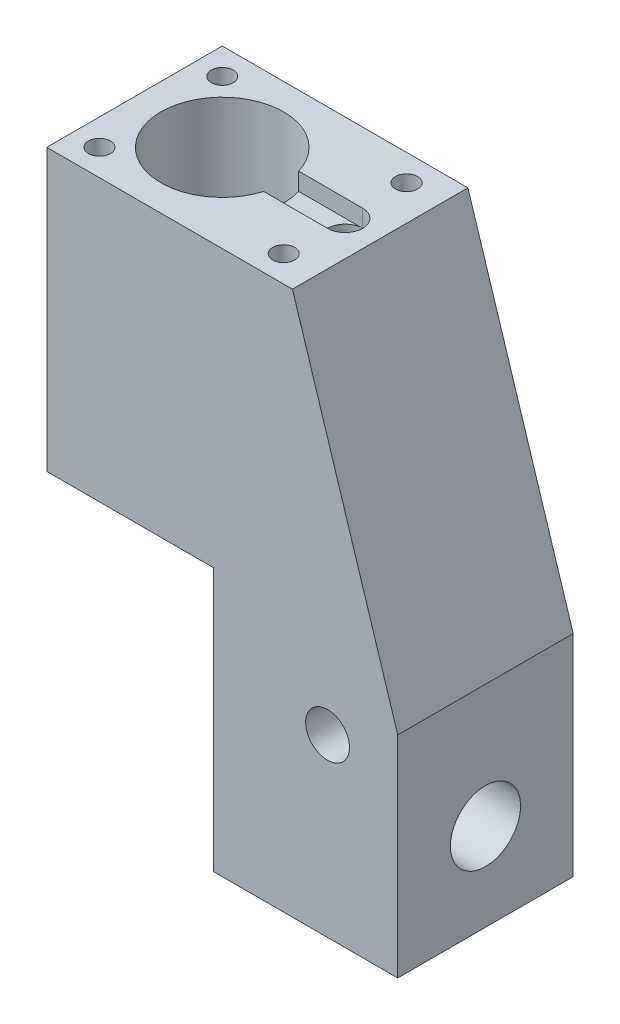
SolidWorks part; units mm, degrees
ref_plane "Front Plane" through (0, 0, 0) normal (0, 0, 1) x (1, 0, 0)
ref_plane "Top Plane" through (0, 0, 0) normal (0, 1, 0) x (1, 0, 0)
ref_plane "Right Plane" through (0, 0, 0) normal (1, 0, 0) x (0, 0, -1)
sketch "Sketch1" plane through (0, 0, 0) normal (0, 0, 1) x (1, 0, 0)
  line L0 (0, 0) -> (-21, 0)
  line L1 (-21, 0) -> (-21, 30)
  line L2 (-21, 30) -> (-40, 30)
  line L3 (-40, 30) -> (-40, 62)
  line L4 (-40, 62) -> (-12, 62)
  line L5 (-12, 62) -> (0, 24)
  line L6 (0, 24) -> (0, 0)
  circle A0 centre (-8, 20) radius 2.5
  point P8 (-30.5, 30)
  dimension "D7" = 5
  dimension "D1" = 62
  dimension "D2" = 21
  dimension "D3" = 30
  dimension "D4" = 38
  dimension "D5" = 40
  dimension "D6" = 12
  dimension "D8" = 8
  dimension "D9" = 20
extrude "Boss-Extrude1" add sketch "Sketch1" along normal mid plane 20
sketch "Sketch2" plane through (0, 62, 0) normal (0, 1, 0) x (1, 0, 0)
  line L0 (4.5122, 0) -> (-49.0895, 0) construction
  line L1 (-40, -10) -> (-40, 10) construction
  line L2 (-16, 2) -> (-23.2918, 2)
  line L3 (-16, -2) -> (-23.2918, -2)
  circle A0 centre (-30, 0) radius 7
  circle A1 centre (-16, 0) radius 2
  dimension "D1" = 14
  dimension "D2" = 4
  dimension "D3" = 10
  dimension "D4" = 24
extrude "Cut-Extrude1" cut sketch "Sketch2" against normal through all contours A0 L0 | L0 A0 region at (-30, 62, 2.9709) region at (-30, 62, -2.9709)
extrude "Cut-Extrude2" cut sketch "Sketch2<3>" against normal blind 2 contours A1 L0 A0 L3 | L0 A1 L2 A0 | L0 A1 | A1 L0 region at (-16, 62, 0.8488) region at (-16, 62, -0.8488) region at (-20.3163, 62, 1.0517) region at (-20.3163, 62, -1.0517)
sketch "Sketch2<3>" plane through (0, 62, 0) normal (0, 1, 0) x (1, 0, 0) same geometry as "Sketch2"
sketch "Sketch3" plane through (0, 62, 0) normal (0, 1, 0) x (1, 0, 0)
  line L0 (-40, -10) -> (-40, 10) construction
  line L1 (-12, 10) -> (-40, 10) construction
  circle A0 centre (-16, 7) radius 1.17
  circle A1 centre (-16, -7) radius 1.4907
  circle A2 centre (-37, -7) radius 1.0297
  circle A3 centre (-37, 7) radius 1.0056
  point P12 (-37.2561, 7.7333)
  point P13 (0, 0)
  point P14 (0, 0)
  point P15 (0, 0)
  dimension "D1" = 3
  dimension "D2" = 24
  dimension "D3" = 14
  dimension "D4" = 3
hole_wizard "M3 Tapped Hole1" positions "Sketch4" profile "Sketch5" tap size "M3" standard "ISO"
sketch "Sketch4" plane through (0, 62, 0) normal (0, 1, 0) x (1, 0, 0)
  point P0 (-37, 7)
  point P3 (-37, -7)
  point P6 (-16, -7)
  point P9 (-16, 7)
sketch "Sketch5" plane through (-37, 62, -7) normal (1, 0, 0) x (0, 0, 1)
  line L0 (0, 0) -> (0, 9.7511)
  line L1 (0, 9.7511) -> (1.25, 9)
  line L2 (1.25, 9) -> (1.25, 0)
  line L5 (1.25, 0) -> (0, 0)
  line L10 (0, 9.7511) -> (-1.25, 9) construction
  line L11 (0, -6.35) -> (0, 107.95) construction
  dimension "Tap Drill Dia." = 2.5
  dimension "Tap Drill Depth" = 9
  dimension "Drill Angle" = 118
cosmetic thread "Hole Thread1" parameters "D1"=6, "D2"=3
cosmetic thread "Hole Thread2" parameters "D1"=6, "D2"=3
cosmetic thread "Hole Thread3" parameters "D1"=6, "D2"=3
cosmetic thread "Hole Thread4" parameters "D1"=6, "D2"=3
sketch "Sketch6" plane through (0, 0, 0) normal (1, 0, 0) x (0, 0, -1)
  line L0 (-10, 0) -> (10, 0) construction
  circle A0 centre (0, 10) radius 4
  dimension "D1" = 8
  dimension "D2" = 10
extrude "Cut-Extrude3" cut sketch "Sketch6" against normal through all
sketch "Sketch7" plane through (0, 0, 0) normal (0, -1, 0) x (1, 0, 0)
  line L0 (6.3741, 0) -> (-47.5245, 0) construction
  line L1 (0, 10) -> (0, -10) construction
  circle A0 centre (-8, 0) radius 1.0826
  circle A1 centre (-16, 0) radius 2.0288
  dimension "D1" = 8
  dimension "D2" = 8
hole_wizard "M4 Tapped Hole1" positions "Sketch8" profile "Sketch9" tap size "M4" standard "ISO" end condition up to next
sketch "Sketch8" plane through (0, 0, 0) normal (0, -1, 0) x (-1, 0, 0)
  point P0 (8, 0)
  point P3 (16, 0)
sketch "Sketch9" plane through (-8, 0, 0) normal (1, 0, 0) x (0, 0, -1)
  line L0 (0, 0) -> (0, 6)
  line L1 (0, 6) -> (1.65, 6)
  line L2 (1.65, 6) -> (1.65, 0.375)
  line L3 (1.65, 0.375) -> (2.025, 0)
  line L5 (2.025, 0) -> (0, 0)
  line L6 (-1.65, 0.375) -> (-2.025, 0) construction
  line L11 (0, -6.35) -> (0, 107.95) construction
  dimension "Thru Tap Drill Dia." = 3.3
  dimension "Thru Tap Drill Depth" = 6
  dimension "Near C'Sink Dia." = 4.05
  dimension "Near C'Sink Angle" = 90
cosmetic thread "Hole Thread7" parameters "D2"=4
cosmetic thread "Hole Thread8" parameters "D2"=4
sketch "Sketch10" plane through (-40, 0, 0) normal (-1, 0, 0) x (0, 0, 1)
  line L0 (0, -3.828) -> (0, 77.3608) construction
  line L2 (10, 62) -> (-10, 62) construction
  circle A0 centre (-3, 45) radius 1.6
  circle A1 centre (3, 45) radius 1.6
  point P9 (1.2131, 54.6335)
  dimension "D1" = 3.2
  dimension "D2" = 6
  dimension "D3" = 17
extrude "Cut-Extrude4" cut sketch "Sketch10" against normal blind 8
sketch "Sketch11" plane through (0, 60, 0) normal (0, 1, 0) x (1, 0, 0)
  circle A0 centre (-16.0052, 0) radius 2
  point P2 (-16.0052, 0)
  dimension "D1" = 4
extrude "Cut-Extrude5" cut sketch "Sketch11" against normal blind 20
sketch "Sketch12" plane through (0, 40, 0) normal (0, 1, 0) x (1, 0, 0)
  circle A0 centre (-16, 0) radius 1
  point P2 (-16, 0)
  dimension "D1" = 2
extrude "Cut-Extrude6" cut sketch "Sketch12" against normal blind 29
